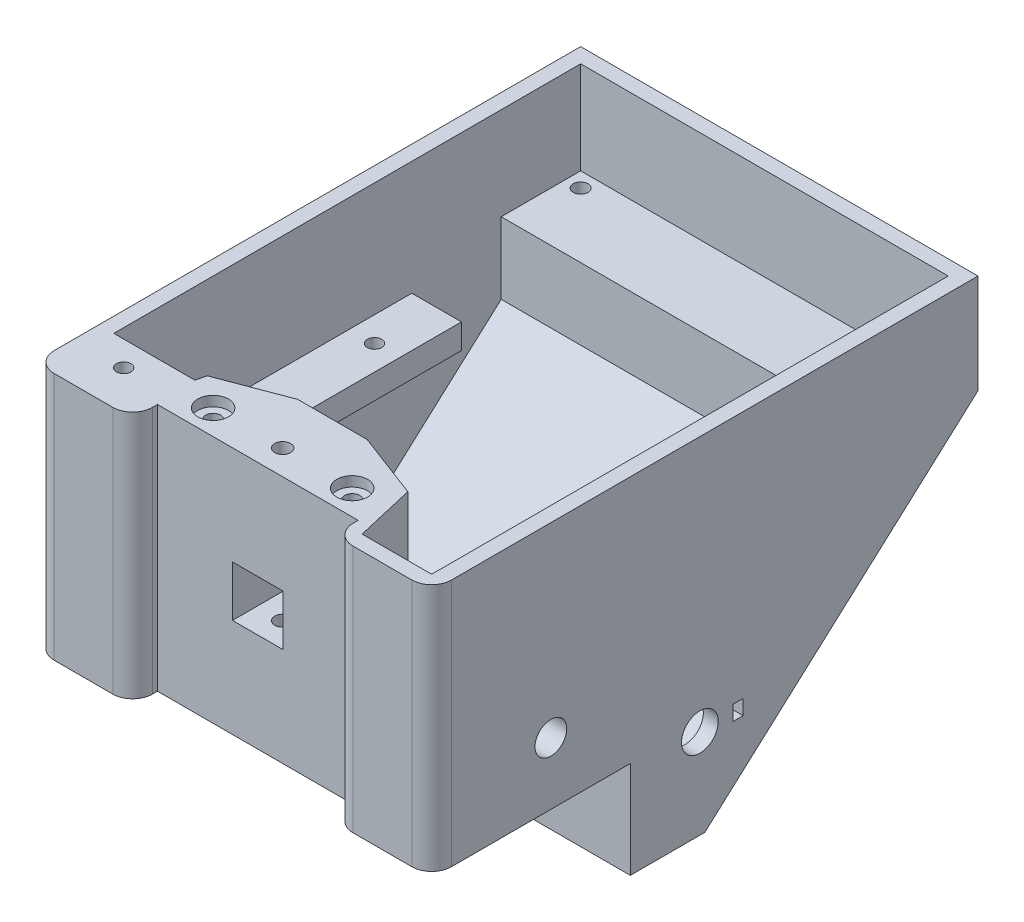
SolidWorks part; units mm, degrees
ref_plane "Спереди" through (0, 0, 0) normal (0, 0, 1) x (1, 0, 0)
ref_plane "Сверху" through (0, 0, 0) normal (0, 1, 0) x (1, 0, 0)
ref_plane "Справа" through (0, 0, 0) normal (1, 0, 0) x (0, 0, -1)
sketch "Sketch2" plane through (0, 0, 0) normal (1, 0, 0) x (0, 0, -1)
  line L0 (-27.3205, 20.9982) -> (-27.3205, -29.0018)
  line L1 (-27.3205, -29.0018) -> (12.6795, -29.0018)
  line L2 (12.6795, -29.0018) -> (12.6795, -48.5114)
  line L3 (12.6795, -48.5114) -> (27.6795, -48.5114)
  line L4 (82.6795, 20.9982) -> (82.6795, 0.9982)
  line L5 (82.6795, 20.9982) -> (-27.3205, 20.9982)
  line L6 (82.6795, 0.9982) -> (27.6795, -48.5114)
  dimension "D1" = 110
  dimension "D2" = 50
  dimension "D3" = 40
  dimension "D4" = 15
  dimension "D5" = 20
extrude "Boss-Extrude1" add sketch "Sketch2" along normal blind 80
shell "Shell1" thickness 3 removed face at (40, 20.9982, -27.6795)
sketch "Sketch3" plane through (0, 0, 24.3205) normal (0, 0, -1) x (-1, 0, 0)
  line L0 (-40, 20.9982) -> (-40, -26.0018) construction
  line L3 (-77, 20.9982) -> (-3, 20.9982) construction
  line L4 (-77, -26.0018) -> (-3, -26.0018) construction
  line L6 (-17, 20.9982) -> (-63, 20.9982)
  line L7 (-17, 20.9982) -> (-17, -26.0018)
  line L8 (-17, -26.0018) -> (-63, -26.0018)
  line L9 (-63, 20.9982) -> (-63, -26.0018)
  line L10 (-17, 20.9982) -> (-63, -26.0018) construction
  line L11 (-17, -26.0018) -> (-63, 20.9982) construction
  point P6 (-40, -2.5018)
  dimension "D1" = 46
extrude "Boss-Extrude2" add sketch "Sketch3" along normal blind 17
sketch "Sketch4" plane through (0, 0, 27.3205) normal (0, 0, 1) x (1, 0, 0)
  line L0 (0, 20.9982) -> (80, -29.0018) construction
  line L2 (45.1, -9.1018) -> (34.9, -9.1018)
  line L3 (45.1, -9.1018) -> (45.1, 1.0982)
  line L4 (45.1, 1.0982) -> (34.9, 1.0982)
  line L5 (34.9, -9.1018) -> (34.9, 1.0982)
  line L6 (45.1, -9.1018) -> (34.9, 1.0982) construction
  line L7 (45.1, 1.0982) -> (34.9, -9.1018) construction
  point P4 (40, -4.0018)
  dimension "D1" = 10.2
extrude "Cut-Extrude1" cut sketch "Sketch4" against normal up to surface (20 mm away) up to face at (40, -2.5018, 7.3205)
sketch "Sketch6" plane through (0, -29.0018, 0) normal (0, -1, 0) x (1, 0, 0)
  line L0 (40, 27.3205) -> (40, -12.6795) construction
  line L1 (47.5, -5.4795) -> (32.5, -5.4795)
  line L2 (47.5, -5.4795) -> (47.5, 7.3205)
  line L3 (47.5, 7.3205) -> (32.5, 7.3205)
  line L4 (32.5, -5.4795) -> (32.5, 7.3205)
  line L5 (47.5, -5.4795) -> (32.5, 7.3205) construction
  line L6 (47.5, 7.3205) -> (32.5, -5.4795) construction
  line L7 (80, -12.6795) -> (0, -12.6795) construction
  line L9 (80, 27.3205) -> (0, 27.3205) construction
  point P0 (40, 0.9205)
  dimension "D1" = 15
  dimension "D2" = 12.8
  dimension "D4" = 20
extrude "Cut-Extrude2" cut sketch "Sketch6" against normal up to surface (3 mm away) up to face at (40, -26.0018, 10.0705)
sketch "Sketch7" plane through (0, 0, 27.3205) normal (0, 0, 1) x (1, 0, 0)
  line L0 (40, 20.9982) -> (40, -29.0018) construction
  line L1 (80, 20.9982) -> (0, 20.9982) construction
  line L2 (80, -29.0018) -> (0, -29.0018) construction
  line L4 (60.2, -29.0018) -> (19.8, -29.0018)
  line L5 (60.2, -29.0018) -> (60.2, 20.9982)
  line L6 (60.2, 20.9982) -> (19.8, 20.9982)
  line L7 (19.8, -29.0018) -> (19.8, 20.9982)
  line L8 (60.2, -29.0018) -> (19.8, 20.9982) construction
  line L9 (60.2, 20.9982) -> (19.8, -29.0018) construction
  point P6 (40, -4.0018)
  dimension "D1" = 40.4
extrude "Cut-Extrude3" cut sketch "Sketch7" against normal blind 5
fillet "Fillet1" radius 4 4 edges at (19.8, -4.0018, 27.3205) (60.2, -4.0018, 27.3205) (80, -4.0018, 27.3205) (0, -4.0018, 27.3205)
sketch "Sketch12" plane through (0, 20.9982, 0) normal (0, 1, 0) x (1, 0, 0)
  line L0 (19.8, -22.3205) -> (19.8, -12.3205) construction
  line L1 (19.8, -12.3205) -> (60.2, -12.3205) construction
  line L2 (60.2, -12.3205) -> (60.2, -22.3205) construction
  line L3 (33, -7.3205) -> (19.8, -12.3205)
  line L4 (17, -7.3205) -> (63, -7.3205) construction
  line L5 (19.8, -12.3205) -> (17, -24.3205)
  line L6 (17, -24.3205) -> (17, -7.3205)
  line L7 (17, -7.3205) -> (33, -7.3205)
  line L8 (47, -7.3205) -> (63, -7.3205)
  line L9 (63, -7.3205) -> (63, -24.3205)
  line L10 (63, -24.3205) -> (60.2, -12.3205)
  line L11 (60.2, -12.3205) -> (47, -7.3205)
  dimension "D1" = 10
  dimension "D2" = 16
extrude "Cut-Extrude7" cut sketch "Sketch12" against normal up to surface (47 mm away) up to face at (40, -26.0018, 7.0205)
sketch "Sketch13" plane through (0, 20.9982, 0) normal (0, 1, 0) x (1, 0, 0)
  line L0 (19.8, -22.3205) -> (19.8, -12.3205) construction
  line L1 (19.8, -12.3205) -> (60.2, -12.3205) construction
  line L2 (60.2, -12.3205) -> (60.2, -22.3205) construction
  line L3 (60.2, -17.3205) -> (19.8, -17.3205) construction
  circle A0 centre (26, -17.3205) radius 1.5
  circle A1 centre (54, -17.3205) radius 1.5
  point P14 (40, -17.3205)
  dimension "D1" = 3
  dimension "D2" = 28
  dimension "D3" = 14
  dimension "D4" = 6.2
extrude "Cut-Extrude8" cut sketch "Sketch13" against normal blind 25
sketch "Sketch14" plane through (0, 20.9982, 0) normal (0, 1, 0) x (1, 0, 0)
  circle A0 centre (26, -17.3205) radius 3.1
  circle A1 centre (54, -17.3205) radius 3.1
  dimension "D1" = 6.2
extrude "Cut-Extrude9" cut sketch "Sketch14" against normal blind 2
sketch "Sketch17" plane through (77, 0, 0) normal (-1, 0, 0) x (0, 0, 1)
  line L0 (-45.6795, -2.0018) -> (-0.6795, -2.0018)
  line L1 (-0.6795, -2.0018) -> (-0.6795, -7.0018)
  line L2 (-0.6795, -7.0018) -> (-45.6795, -7.0018)
  line L3 (-45.6795, -7.0018) -> (-45.6795, -2.0018)
  line L4 (-79.6795, 20.9982) -> (24.3205, 20.9982) construction
  line L5 (-79.6795, 2.3342) -> (-79.6795, 20.9982) construction
  dimension "D1" = 45
  dimension "D2" = 5
  dimension "D3" = 23
  dimension "D4" = 34
extrude "Boss-Extrude5" add sketch "Sketch17" along normal up to surface (74 mm away) up to face at (3, -14.0994, -24.0865)
sketch "Sketch18" plane through (0, -2.0018, 0) normal (0, 1, 0) x (1, 0, 0)
  line L0 (40, 0.6795) -> (40, 45.6795) construction
  line L1 (3, 0.6795) -> (77, 0.6795) construction
  line L2 (3, 45.6795) -> (77, 45.6795) construction
  line L3 (77, 0.6795) -> (77, 45.6795) construction
  line L4 (13, 0.6795) -> (67, 0.6795)
  line L5 (13, 0.6795) -> (13, 45.6795)
  line L6 (13, 45.6795) -> (67, 45.6795)
  line L7 (67, 0.6795) -> (67, 45.6795)
  line L8 (13, 0.6795) -> (67, 45.6795) construction
  line L9 (13, 45.6795) -> (67, 0.6795) construction
  point P6 (40, 23.1795)
  dimension "D1" = 10
extrude "Cut-Extrude10" cut sketch "Sketch18" against normal up to next
sketch "Sketch19" plane through (0, -2.0018, 0) normal (0, 1, 0) x (1, 0, 0)
  line L0 (72, 45.6795) -> (72, 0.6795) construction
  line L1 (67, 45.6795) -> (77, 45.6795) construction
  line L2 (67, 0.6795) -> (77, 0.6795) construction
  line L3 (8, 45.6795) -> (8, 0.6795) construction
  line L4 (3, 45.6795) -> (13, 45.6795) construction
  line L5 (3, 0.6795) -> (13, 0.6795) construction
  circle A0 centre (72, 37.1795) radius 1.45
  circle A1 centre (72, 6.1795) radius 1.45
  circle A2 centre (8, 33.1795) radius 1.45
  circle A3 centre (8, 6.1795) radius 1.45
  point P20 (72, 23.1795)
  point P21 (8, 23.1795)
  dimension "D1" = 2.9
  dimension "D2" = 14
  dimension "D3" = 17
  dimension "D4" = 17
  dimension "D5" = 10
extrude "Cut-Extrude11" cut sketch "Sketch19" against normal up to next
sketch "Sketch21" plane through (0, -26.0018, 0) normal (0, 1, 0) x (1, 0, 0)
  line L0 (3, -24.3205) -> (3, -14.3205)
  line L1 (3, -24.3205) -> (3, 15.6795) construction
  line L2 (3, -14.3205) -> (19.3333, -14.3205)
  line L3 (19.8, -12.3205) -> (17, -24.3205) construction
  line L4 (19.3333, -14.3205) -> (17, -24.3205)
  line L6 (3, -24.3205) -> (17, -24.3205)
  dimension "D1" = 10
extrude "Boss-Extrude6" add sketch "Sketch21" along normal up to surface (47 mm away) up to face at (54, 20.9982, 20.4205)
sketch "Sketch22" plane through (0, 20.9982, 0) normal (0, 1, 0) x (1, 0, 0)
  line L0 (0, 82.6795) -> (0, -23.3205) construction
  line L1 (15.8, -27.3205) -> (4, -27.3205) construction
  circle A0 centre (10, -19.3205) radius 1.45
  dimension "D1" = 2.9
  dimension "D2" = 10
  dimension "D3" = 8
extrude "Cut-Extrude12" cut sketch "Sketch22" against normal through all
sketch "Sketch24" plane through (80, 0, 0) normal (1, 0, 0) x (0, 0, -1)
  line L0 (12.6795, -48.5114) -> (27.6795, -48.5114) construction
  line L1 (12.6795, -29.0018) -> (12.6795, -48.5114) construction
  line L2 (18.1795, -30.5114) -> (18.1795, -19.0114) construction
  line L3 (18.1795, -19.0114) -> (35.1795, -19.0114) construction
  line L4 (35.1795, -19.0114) -> (35.1795, -30.5114) construction
  line L5 (26.6795, -19.0114) -> (26.6795, -39.0114) construction
  line L6 (30.3795, -30.5114) -> (34.3795, -30.5114) construction
  line L8 (33.3795, -32.0114) -> (35.3795, -32.0114)
  line L9 (33.3795, -32.0114) -> (33.3795, -29.0114)
  line L10 (33.3795, -29.0114) -> (35.3795, -29.0114)
  line L11 (35.3795, -32.0114) -> (35.3795, -29.0114)
  line L12 (33.3795, -32.0114) -> (35.3795, -29.0114) construction
  line L13 (33.3795, -29.0114) -> (35.3795, -32.0114) construction
  circle A0 centre (26.6795, -30.5114) radius 3.7
  circle A1 centre (26.6795, -30.5114) radius 8.5 construction
  dimension "D1" = 7.4
  dimension "D2" = 17
  dimension "D3" = 18
  dimension "D4" = 14
  dimension "D5" = 20
  dimension "D6" = 4
  dimension "D7" = 2
  dimension "D8" = 3
extrude "Cut-Extrude13" cut sketch "Sketch24" against normal through all
sketch "Sketch26" plane through (3, 0, 0) normal (1, 0, 0) x (0, 0, -1)
  line L0 (79.6795, 2.3342) -> (63.6795, 2.3342)
  line L1 (63.6795, 2.3342) -> (63.6795, -12.0686)
  line L2 (26.5281, -45.5114) -> (79.6795, 2.3342) construction
  line L3 (63.6795, -12.0686) -> (79.6795, 2.3342)
  dimension "D1" = 16
extrude "Boss-Extrude7" add sketch "Sketch26" along normal up to surface (74 mm away) up to face at (77, -30.5114, -34.3795)
sketch "Sketch27" plane through (0, 2.3342, 0) normal (0, 1, 0) x (1, 0, 0)
  line L0 (3, 76.6795) -> (77, 76.6795) construction
  line L1 (3, 79.6795) -> (3, 63.6795) construction
  line L2 (77, 79.6795) -> (77, 63.6795) construction
  line L3 (80, 82.6795) -> (0, 82.6795) construction
  circle A0 centre (6, 76.6795) radius 1.5
  circle A1 centre (74, 76.6795) radius 1.5
  point P10 (40, 76.6795)
  dimension "D1" = 3
  dimension "D2" = 68
  dimension "D3" = 34
  dimension "D4" = 6
extrude "Cut-Extrude14" cut sketch "Sketch27" against normal blind 10
sketch "Sketch28" plane through (0, 2.3342, 0) normal (0, 1, 0) x (1, 0, 0)
  line L1 (74, 79.9295) -> (71.1854, 78.3045)
  line L2 (71.1854, 78.3045) -> (71.1854, 75.0545)
  line L3 (71.1854, 75.0545) -> (74, 73.4295)
  line L4 (74, 73.4295) -> (76.8146, 75.0545)
  line L5 (76.8146, 75.0545) -> (76.8146, 78.3045)
  line L6 (76.8146, 78.3045) -> (74, 79.9295)
  line L7 (6, 73.4295) -> (8.8146, 75.0545)
  line L8 (8.8146, 75.0545) -> (8.8146, 78.3045)
  line L9 (8.8146, 78.3045) -> (6, 79.9295)
  line L10 (6, 79.9295) -> (3.1854, 78.3045)
  line L11 (3.1854, 78.3045) -> (3.1854, 75.0545)
  line L12 (3.1854, 75.0545) -> (6, 73.4295)
  circle A0 centre (74, 76.6795) radius 3.25 construction
  circle A1 centre (6, 76.6795) radius 3.25 construction
  dimension "D1" = 6.5
extrude "Cut-Extrude15" cut sketch "Sketch28" against normal blind 32 from offset 3 offset against normal yes
sketch "Sketch29" plane through (0, -29.0018, 0) normal (0, -1, 0) x (1, 0, 0)
  line L0 (0, 23.3205) -> (0, -12.6795) construction
  line L1 (7.1854, 17.6955) -> (10, 16.0705)
  line L2 (10, 16.0705) -> (12.8146, 17.6955)
  line L3 (12.8146, 17.6955) -> (12.8146, 20.9455)
  line L4 (12.8146, 20.9455) -> (10, 22.5705)
  line L5 (10, 22.5705) -> (7.1854, 20.9455)
  line L6 (7.1854, 20.9455) -> (7.1854, 17.6955)
  circle A0 centre (10, 19.3205) radius 3.25 construction
  dimension "D1" = 6.5
extrude "Cut-Extrude16" cut sketch "Sketch29" against normal blind 30
sketch "Sketch30" plane through (0, -26.0018, 0) normal (0, 1, 0) x (1, 0, 0)
  line L0 (77, -24.3205) -> (63, -24.3205)
  line L1 (63, -24.3205) -> (60.2, -12.3205)
  line L2 (63, -24.3205) -> (60.2, -12.3205) construction
  line L3 (60.2, -12.3205) -> (77, -12.3205)
  line L4 (77, -24.3205) -> (77, 15.6795) construction
  line L5 (77, -12.3205) -> (77, -24.3205)
  dimension "D1" = 12
extrude "Boss-Extrude8" add sketch "Sketch30" along normal blind 20
sketch "Sketch31" plane through (0, -6.0018, 0) normal (0, 1, 0) x (1, 0, 0)
  line L0 (76, -27.3205) -> (64.2, -27.3205) construction
  line L1 (80, -23.3205) -> (80, 12.6795) construction
  circle A0 centre (72, -21.3205) radius 1.5
  dimension "D3" = 3
  dimension "D1" = 6
  dimension "D2" = 8
extrude "Cut-Extrude17" cut sketch "Sketch31" against normal through all
sketch "Sketch32" plane through (0, -29.0018, 0) normal (0, -1, 0) x (1, 0, 0)
  line L1 (72, 24.5705) -> (69.1854, 22.9455)
  line L2 (69.1854, 22.9455) -> (69.1854, 19.6955)
  line L3 (69.1854, 19.6955) -> (72, 18.0705)
  line L4 (72, 18.0705) -> (74.8146, 19.6955)
  line L5 (74.8146, 19.6955) -> (74.8146, 22.9455)
  line L6 (74.8146, 22.9455) -> (72, 24.5705)
  circle A0 centre (72, 21.3205) radius 3.25 construction
  dimension "D1" = 6.5
extrude "Cut-Extrude18" cut sketch "Sketch32" against normal blind 15
sketch "Sketch33" plane through (0, -2.0018, 0) normal (0, 1, 0) x (1, 0, 0)
  line L0 (67, 40.6795) -> (77, 40.6795)
  line L1 (67, 0.6795) -> (67, 45.6795) construction
  line L2 (77, 0.6795) -> (77, 45.6795) construction
  line L3 (77, 40.6795) -> (77, 45.6795)
  line L4 (77, 45.6795) -> (67, 45.6795)
  line L5 (67, 45.6795) -> (67, 40.6795)
  dimension "D1" = 5
extrude "Cut-Extrude19" cut sketch "Sketch33" against normal up to next
sketch "Sketch34" plane through (0, 20.9982, 0) normal (0, 1, 0) x (1, 0, 0)
  line L0 (54, -17.3205) -> (26, -17.3205) construction
  circle A0 centre (40, -17.3205) radius 1.6
  dimension "D1" = 3.2
extrude "Cut-Extrude20" cut sketch "Sketch34" against normal through all
sketch "Sketch36" plane through (0, -29.0018, 0) normal (0, -1, 0) x (1, 0, 0)
  line L1 (38.375, 20.1351) -> (36.75, 17.3205)
  line L2 (36.75, 17.3205) -> (38.375, 14.5059)
  line L3 (38.375, 14.5059) -> (41.625, 14.5059)
  line L4 (41.625, 14.5059) -> (43.25, 17.3205)
  line L5 (43.25, 17.3205) -> (41.625, 20.1351)
  line L6 (41.625, 20.1351) -> (38.375, 20.1351)
  circle A0 centre (40, 17.3205) radius 3.25 construction
  dimension "D1" = 6.5
extrude "Cut-Extrude22" cut sketch "Sketch36" against normal blind 14
sketch "Sketch37" plane through (80, 0, 0) normal (1, 0, 0) x (0, 0, -1)
  line L0 (-23.3205, -16.5114) -> (63.2281, -16.5114) construction
  line L1 (-23.3205, 20.9982) -> (-23.3205, -29.0018) construction
  line L2 (27.6795, -48.5114) -> (82.6795, 0.9982) construction
  line L3 (30.3795, -30.5114) -> (22.9795, -30.5114) construction
  circle A0 centre (-3.3205, -16.5114) radius 3.2
  circle A1 centre (26.6795, -30.5114) radius 3.7 construction
  point P14 (26.6795, -30.5114)
  dimension "D1" = 6.4
  dimension "D2" = 14
  dimension "D3" = 20
extrude "Cut-Extrude23" cut sketch "Sketch37" against normal up to next
sketch "Sketch38" plane through (77, 0, 0) normal (-1, 0, 0) x (0, 0, 1)
  line L0 (12.3205, -26.0018) -> (-15.6795, -26.0018) construction
  line L1 (8.3205, -7.021) -> (-1.6795, -7.021)
  line L2 (8.3205, -7.021) -> (8.3205, -26.0018)
  line L3 (8.3205, -26.0018) -> (-1.6795, -26.0018)
  line L4 (-1.6795, -7.021) -> (-1.6795, -26.0018)
  line L5 (8.3205, -7.021) -> (-1.6795, -26.0018) construction
  line L6 (8.3205, -26.0018) -> (-1.6795, -7.021) construction
  circle A0 centre (3.3205, -16.5114) radius 3.2
  point P0 (3.3205, -16.5114)
  dimension "D1" = 10
extrude "Boss-Extrude9" add sketch "Sketch38" along normal blind 3
